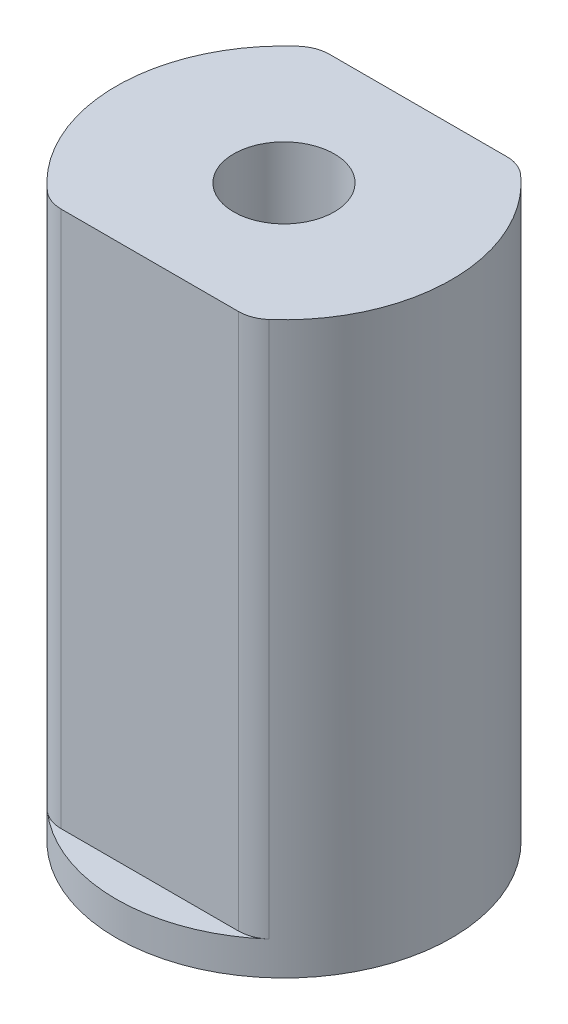
SolidWorks part; units mm, degrees
ref_plane "Front Plane" through (0, 0, 0) normal (0, 0, 1) x (1, 0, 0)
ref_plane "Top Plane" through (0, 0, 0) normal (0, 1, 0) x (1, 0, 0)
ref_plane "Right Plane" through (0, 0, 0) normal (1, 0, 0) x (0, 0, -1)
sketch "Sketch2" plane through (0, 0, 0) normal (0, 1, 0) x (1, 0, 0)
  circle A0 centre (0, 0) radius 2.5
  dimension "D1" = 5
extrude "Boss-Extrude1" add sketch "Sketch2" along normal blind 0.5
sketch "Sketch3" plane through (0, 0.5, 0) normal (0, 1, 0) x (1, 0, 0)
  line L0 (-1.5, 2) -> (1.5, 2)
  line L1 (-2.5, 0) -> (2.5, 0) construction
  line L2 (-1.5, -2) -> (1.5, -2)
  circle A0 centre (0, 0) radius 0.75
  circle A1 centre (0, 0) radius 2.5
  circle A2 centre (0, 0) radius 2.5
  circle M2 centre (0, 0) radius 2.5
  dimension "D3" = 1.5
  dimension "D2" = 2
  dimension "D1" = 0
extrude "Boss-Extrude2" add sketch "Sketch3" along normal blind 8 contours L1 A0 A2 L0 M2 | L1 A2 L2 A0 M2 region at (0, 0.5, -0.9966) region at (0, 0.5, 0.9966)
fillet "Fillet1" radius 0.5 4 edges
